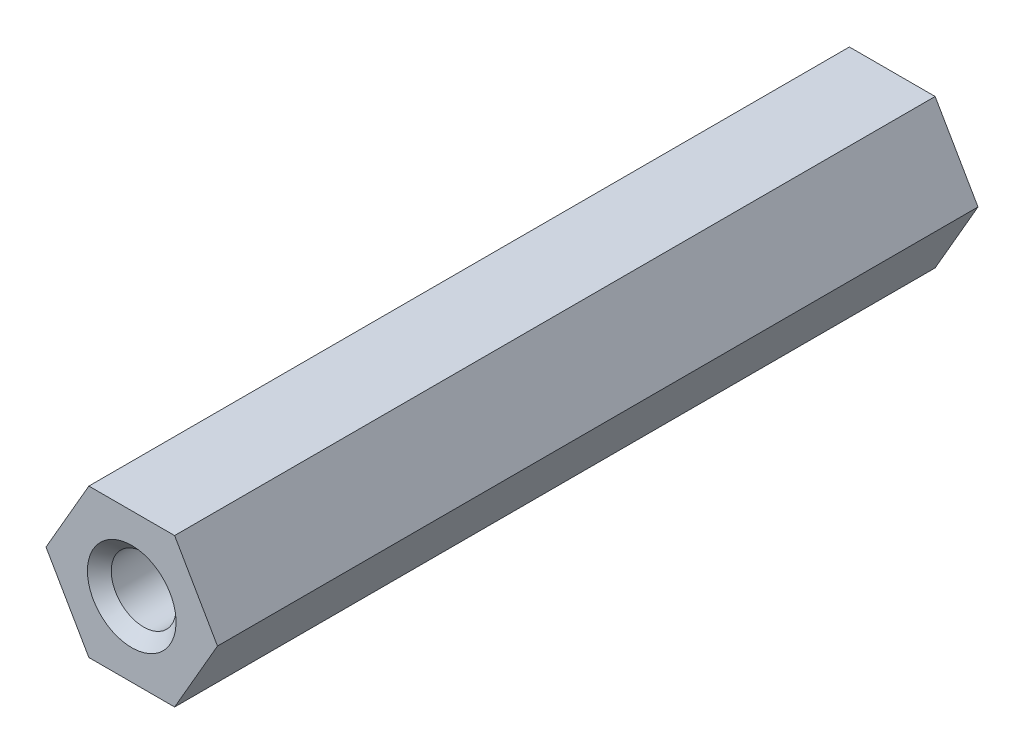
SolidWorks part; units mm, degrees
material "6061-T6 (SS)"
ref_plane "Front" through (0, 0, 0) normal (0, 0, 1) x (1, 0, 0)
ref_plane "Top" through (0, 0, 0) normal (0, 1, 0) x (1, 0, 0)
ref_plane "Right" through (0, 0, 0) normal (1, 0, 0) x (0, 0, -1)
ref_axis "side-side" through (80.9, 0, 0) along (-1, 0, 0)
ref_axis "up-down" through (0, 50, 0) along (0, -1, 0)
ref_axis "front-back" through (0, 0, -80.9) along (0, 0, 1)
sketch "Sketch1" plane through (0, 0, 0) normal (0, 0, 1) x (1, 0, 0)
  line L12 (-3.5796, 0) -> (-1.7898, -3.1)
  line L13 (-1.7898, 3.1) -> (-3.5796, 0)
  line L14 (1.7898, 3.1) -> (-1.7898, 3.1)
  line L15 (3.5796, 0) -> (1.7898, 3.1)
  line L16 (1.7898, -3.1) -> (3.5796, 0)
  line L17 (-1.7898, -3.1) -> (1.7898, -3.1)
extrude "Boss-Extrude1" add sketch "Sketch1" along normal blind 31.75 separate body
hole_wizard "#6-32 Tapped Hole1" positions "Sketch2" profile "Sketch3" tap size "#6-32" standard "ANSI Inch" end condition through all
sketch "Sketch2" plane through (0, 0, 0) normal (0, 0, -1) x (-1, 0, 0)
  point P0 (0, 0)
sketch "Sketch3" plane through (0, 0, 0) normal (1, 0, 0) x (0, 1, 0)
  line L0 (0, 0) -> (0, 31.75)
  line L1 (0, 31.75) -> (1.85, 31.75)
  line L2 (1.3525, 31.2526) -> (1.3525, 0.4974)
  line L3 (1.3525, 0.4974) -> (1.85, 0)
  line L5 (1.85, 0) -> (0, 0)
  line L6 (-1.3525, 0.4974) -> (-1.85, 0) construction
  line L7 (1.85, 31.75) -> (1.3525, 31.2526)
  line L8 (-1.85, 31.75) -> (-1.3526, 31.2526) construction
  line L11 (0, -6.35) -> (0, 107.95) construction
  dimension "Thread Major Dia." = 2.7051
  dimension "Thru Tap Drill Depth" = 31.75
  dimension "Near C'Sink Dia." = 3.7
  dimension "Near C'Sink Angle" = 90
  dimension "Far C'Sink Dia." = 3.7
  dimension "Far C'Sink Angle" = 90
